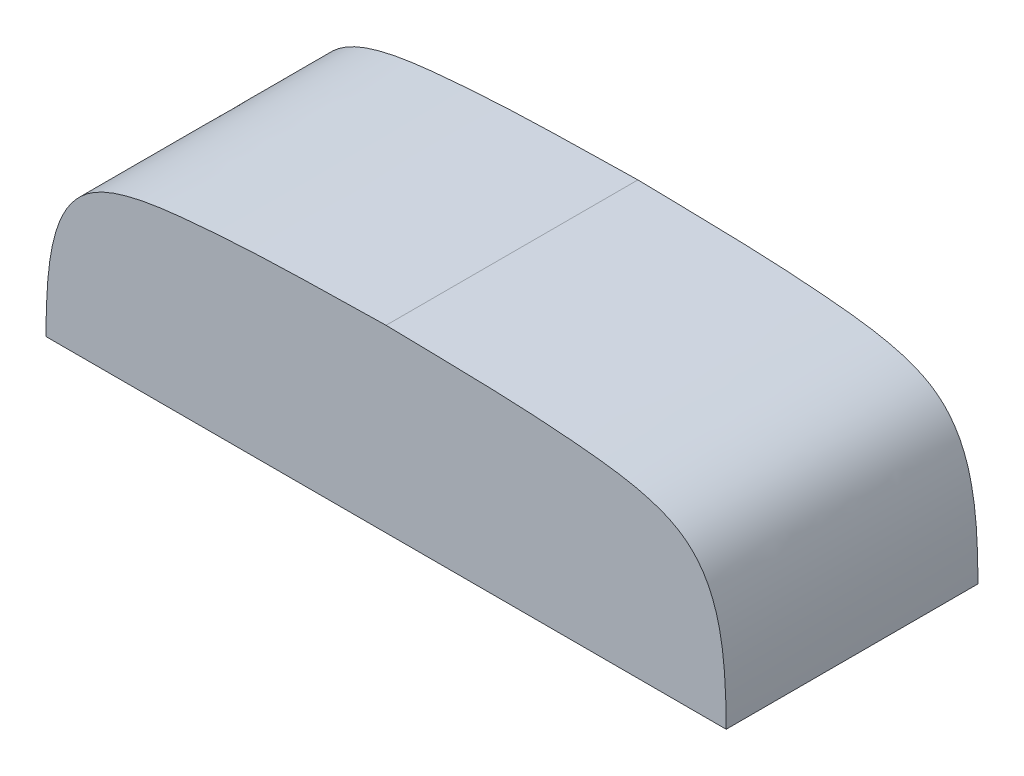
SolidWorks part; units mm, degrees
ref_plane "Front Plane" through (0, 0, 0) normal (0, 0, 1) x (1, 0, 0)
ref_plane "Top Plane" through (0, 0, 0) normal (0, 1, 0) x (1, 0, 0)
ref_plane "Right Plane" through (0, 0, 0) normal (1, 0, 0) x (0, 0, -1)
sketch "Sketch1" plane through (0, 0, 0) normal (0, 0, 1) x (1, 0, 0)
  line L2 (0, 265.0008) -> (0, -43.3016) construction
  line L3 (343.0467, 50.8638) -> (-343.0467, 50.8638)
  spline S0 degree 3 poles (0, 232.2583) (64.9766, 230.6298) (157.6161, 231.0971) (335.026, 207.3029) (342.768, 116.1788) (343.0467, 50.8638) knots 0 0 0 0 0.225226 0.33784 0.524743 0.524743 0.524743 0.524743
  spline S1 degree 3 poles (0, 232.2583) (-64.9766, 230.6298) (-157.6161, 231.0971) (-335.026, 207.3029) (-342.768, 116.1788) (-343.0467, 50.8638) knots 0 0 0 0 0.225226 0.33784 0.524743 0.524743 0.524743 0.524743
  point P7 (346.0352, 51.6215)
  point P8 (0, 0.0638)
  point P12 (0, 0)
  point P15 (-345.8011, 53.284)
  dimension "D2" = 50.8
extrude "Boss-Extrude1" add sketch "Sketch1" along normal blind 127 and the other way blind 127
